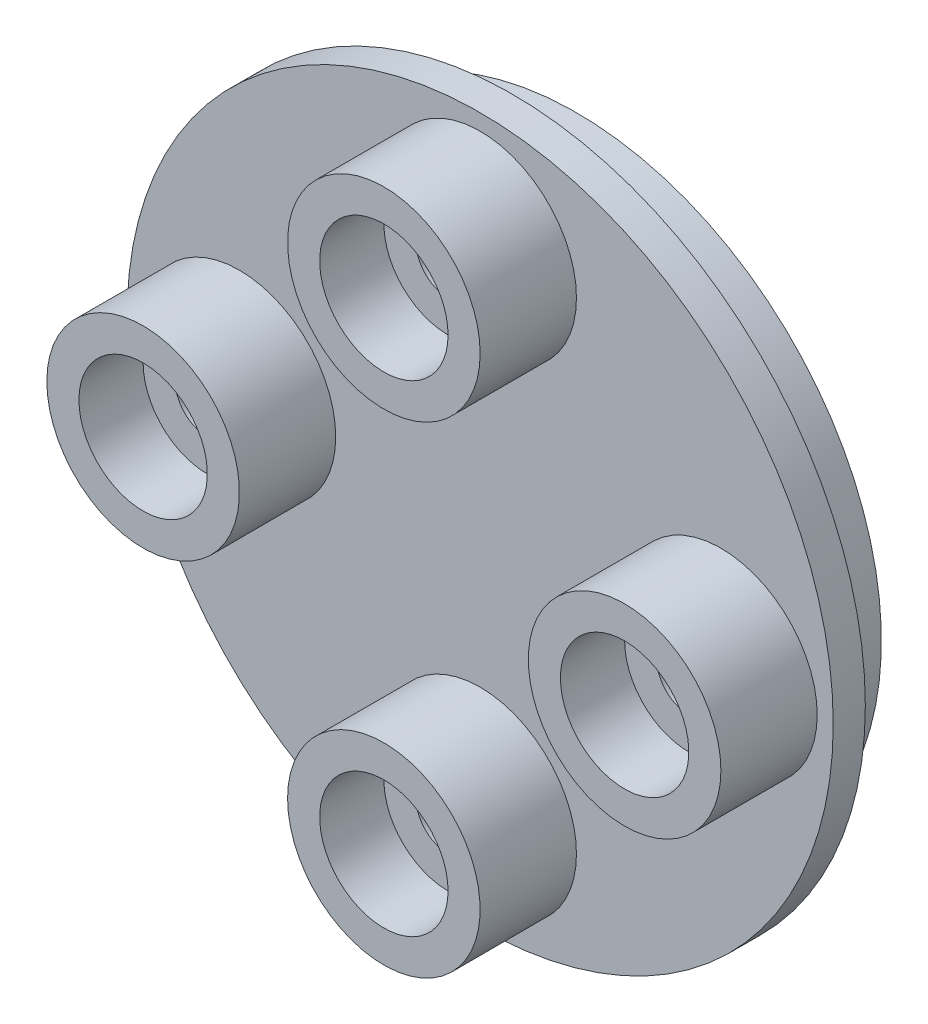
SolidWorks part; units mm, degrees
material "Ceramic Porcelain"
ref_plane "Front Plane" through (0, 0, 0) normal (0, 0, 1) x (1, 0, 0)
ref_plane "Top Plane" through (0, 0, 0) normal (0, 1, 0) x (1, 0, 0)
ref_plane "Right Plane" through (0, 0, 0) normal (1, 0, 0) x (0, 0, -1)
sketch "Sketch1" plane through (0, 0, 0) normal (0, 0, 1) x (1, 0, 0)
  line L0 (-12.5035, 0) -> (16.2542, 0) construction
  line L1 (0, 13.6622) -> (0, -11.4832) construction
  line L2 (0, 0) -> (-13.9777, 13.9777) construction
  circle A0 centre (0, 0) radius 11
  circle A1 centre (0, 0) radius 7.5
  circle A2 centre (0, 7.5) radius 3
  circle A6 centre (0, -7.5) radius 3
  circle A7 centre (-7.5, 0) radius 3
  circle A8 centre (7.5, 0) radius 3
  circle A9 centre (0, 0) radius 11
  dimension "D1" = 22
  dimension "D2" = 15
  dimension "D3" = 6
  dimension "D4" = 45
extrude "Boss-Extrude3" add sketch "Sketch1" along normal blind 4 contours A2 | A7 | A6 | A8
sketch "Sketch5" plane through (0, 0, 4) normal (0, 0, 1) x (1, 0, 0)
  line L0 (0, 0) -> (0, 12.4716) construction
  line L1 (0, 12.4716) -> (0, -13.0128) construction
  line L2 (0, 0) -> (-9.4373, 9.4373) construction
  line L3 (-9.4373, 9.4373) -> (9.9045, -9.9045) construction
  line L4 (0, 0) -> (-17.4196, 0) construction
  line L5 (-17.4196, 0) -> (17.1198, 0) construction
  line L6 (0, 0) -> (-13.2797, -13.2797) construction
  line L7 (-13.2797, -13.2797) -> (11.9909, 11.9909) construction
  circle A0 centre (0, 7.5) radius 3
  circle A1 centre (0, -7.5) radius 3
  circle A2 centre (-7.5, 0) radius 3
  circle A3 centre (7.5, 0) radius 3
  circle A4 centre (-7.5, 0) radius 1
  circle A5 centre (0, 7.5) radius 1
  circle A6 centre (0, -7.5) radius 1
  circle A7 centre (7.5, 0) radius 1
  circle A8 centre (0, 7.5) radius 2
  circle A9 centre (7.5, 0) radius 2
  circle A10 centre (0, -7.5) radius 2
  circle A11 centre (-7.5, 0) radius 2
  arc A12 (-7.5, 0) -> (0, -7.5) centre (0, 0) ccw construction
  dimension "D1" = 2
extrude "Boss-Extrude9" add sketch "Sketch1<6>" along normal blind 1 contours A0 A8 A1 A6 A7 A2 | A8 A1 A2 A7 A6 region at (-10.6889, 0, 0) region at (0, 0, 0)
sketch "Sketch1<6>" plane through (0, 0, 0) normal (0, 0, 1) x (1, 0, 0) same geometry as "Sketch1"
extrude "Cut-Extrude5" cut sketch "Sketch5" against normal blind 2 contours A11 | A8 | A9 | A10
sketch "Sketch9" plane through (0, 0, 0) normal (0, 0, -1) x (-1, 0, 0)
  circle A1 centre (0, 0) radius 9.5
  dimension "D1" = 19
sketch "Sketch11" plane through (0, 0, 2) normal (0, 0, 1) x (1, 0, 0)
  line L0 (0, 0) -> (-10.5102, 10.5102) construction
  line L1 (0, 0) -> (10.1888, 10.1888) construction
  circle A1 centre (0, 7.5) radius 1
  circle A2 centre (-7.5, 0) radius 1
  circle A3 centre (0, -7.5) radius 1
  circle A4 centre (7.5, 0) radius 1
extrude "Boss-Extrude17" add sketch "Sketch9" along normal blind 2 and the other way blind 0.0001
sketch "Sketch24" plane through (0, 0, -2) normal (0, 0, -1) x (-1, 0, 0)
  circle A0 centre (0, 0) radius 9
  dimension "D1" = 18
extrude "Cut-Extrude11" cut sketch "Sketch24" against normal blind 1 from offset 0.5 offset against normal yes
sketch "Sketch26" plane through (0, 0, -2) normal (0, 0, -1) x (-1, 0, 0)
  circle A0 centre (0, 0) radius 1
  dimension "D1" = 2
fillet "Fillet10" radius 1 1 edges at (9.5, 0, 0)
extrude "Cut-Extrude13" cut sketch "Sketch11" against normal blind 2.5
sketch "Sketch29" plane through (0, 0, 0) normal (1, 0, 0) x (0, 0, -1)
  line L0 (2, 0) -> (10.6422, 0) construction
  line L1 (2, -9.5) -> (2, 9.5) construction
  line L2 (2, 0) -> (2, 2)
  line L3 (2, 2) -> (5.5, 1.5)
  line L4 (5.5, 1.5) -> (5.5, 0)
  line L5 (2, 0) -> (5.5, 0)
  dimension "D1" = 3.5
  dimension "D2" = 1.5
  dimension "D3" = 2
revolve "Revolve3" add sketch "Sketch29" angle 360 about L0
extrude "Cut-Extrude14" cut sketch "Sketch26" along normal through all from offset 1 offset against normal yes
fillet "Fillet11" radius 1 1 edges at (2, 0, -2)
